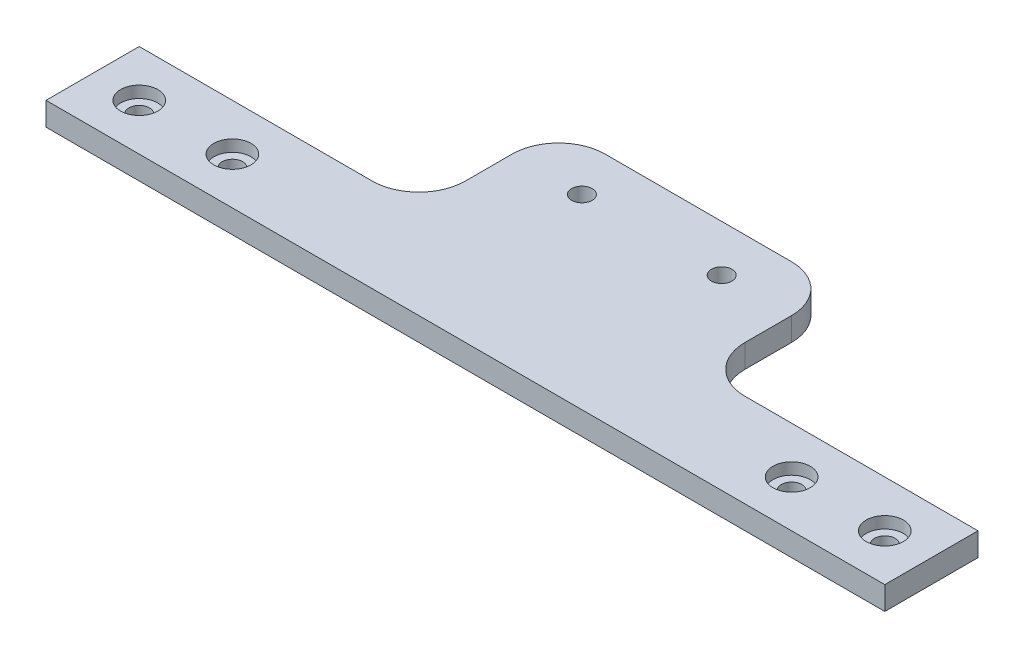
SolidWorks part; units mm, degrees
ref_plane "Front" through (0, 0, 0) normal (0, 0, 1) x (1, 0, 0)
ref_plane "Top" through (0, 0, 0) normal (0, 1, 0) x (1, 0, 0)
ref_plane "Right" through (0, 0, 0) normal (1, 0, 0) x (0, 0, -1)
sketch "Sketch1" plane through (0, 0, 0) normal (0, 1, 0) x (1, 0, 0)
  line L1 (0, 0) -> (406.4, 0)
  line L2 (0, 0) -> (0, 25.4)
  line L3 (0, 25.4) -> (406.4, 25.4)
  line L4 (406.4, 0) -> (406.4, 25.4)
  line L5 (165.1, 25.4) -> (241.3, 25.4)
  line L6 (165.1, 25.4) -> (165.1, 63.5)
  line L7 (165.1, 63.5) -> (241.3, 63.5)
  line L8 (241.3, 25.4) -> (241.3, 63.5)
  dimension "D1" = 406.4
  dimension "D2" = 25.4
  dimension "D3" = 76.2
  dimension "D4" = 165.1
  dimension "D5" = 38.1
extrude "Boss-Extrude1" add sketch "Sketch1" along normal blind 6.35 contours L1 L4 L3 L2 | L3 L8 L7 L6 region at (203.2, 0, -12.7) region at (203.2, 0, -44.45)
sketch "Sketch3" plane through (0, 6.35, 0) normal (0, 1, 0) x (1, 0, 0)
  line L0 (241.3, 25.4) -> (406.4, 25.4) construction
  line L2 (0, 0) -> (406.4, 0) construction
  circle A0 centre (222.25, 50.8) radius 2.794
  circle A1 centre (184.15, 50.8) radius 2.794
  point P6 (203.2, 0)
  dimension "D1" = 25.4
  dimension "D3" = 38.1
  dimension "D2" = 19.05
extrude "Cut-Extrude2" cut sketch "Sketch3" against normal up to surface (6.35 mm away) up to face at (203.2, 0, -28.575)
fillet "Fillet1" radius 12.7 8 edges at (406.4, 3.175, 0) (406.4, 3.175, -25.4) (0, 3.175, 0) (0, 3.175, -25.4) (165.1, 3.175, -25.4) (241.3, 3.175, -25.4) (241.3, 3.175, -63.5) (165.1, 3.175, -63.5)
sketch "Sketch4" plane through (0, 6.35, 0) normal (0, 1, 0) x (1, 0, 0)
  line L0 (12.7, 0) -> (393.7, 0) construction
  circle A0 centre (279.4, 12.7) radius 2.794
  circle A1 centre (304.8, 12.7) radius 2.794
  circle A3 centre (127, 12.7) radius 2.794
  circle A4 centre (101.6, 12.7) radius 2.794
  point P4 (203.2, 0)
  dimension "D1" = 76.2
  dimension "D2" = 25.4
  dimension "D3" = 152.4
  dimension "D4" = 25.4
extrude "Cut-Extrude3" cut sketch "Sketch4" against normal blind 19.05 from surface starting at face at (222.25, 6.35, -48.006)
sketch "Sketch5" plane through (0, 6.35, 0) normal (0, 1, 0) x (1, 0, 0)
  circle A0 centre (101.6, 12.7) radius 5.08
  circle A1 centre (127, 12.7) radius 5.08
  circle A2 centre (279.4, 12.7) radius 5.08
  circle A3 centre (304.8, 12.7) radius 5.08
extrude "Cut-Extrude4" cut sketch "Sketch5" against normal blind 3.175
sketch "Sketch6" plane through (0, 6.35, 0) normal (0, 1, 0) x (1, 0, 0)
  line L0 (12.7, 25.4) -> (152.4, 25.4) construction
  line L1 (88.9, 25.4) -> (0, 25.4)
  line L2 (88.9, 25.4) -> (88.9, 0)
  line L3 (88.9, 0) -> (0, 0)
  line L4 (0, 25.4) -> (0, 0)
  line L5 (177.8, 63.5) -> (228.6, 63.5) construction
  line L6 (254, 25.4) -> (393.7, 25.4) construction
  line L7 (317.5, 25.4) -> (406.4, 25.4)
  line L8 (317.5, 25.4) -> (317.5, 0)
  line L9 (317.5, 0) -> (406.4, 0)
  line L10 (406.4, 25.4) -> (406.4, 0)
  point P8 (203.2, 63.5)
  dimension "D1" = 114.3
  dimension "D2" = 88.9
  dimension "D3" = 114.3
  dimension "D4" = 88.9
extrude "Cut-Extrude5" cut sketch "Sketch6" against normal up to surface (6.35 mm away) up to face at (101.6, 0, -9.906)
